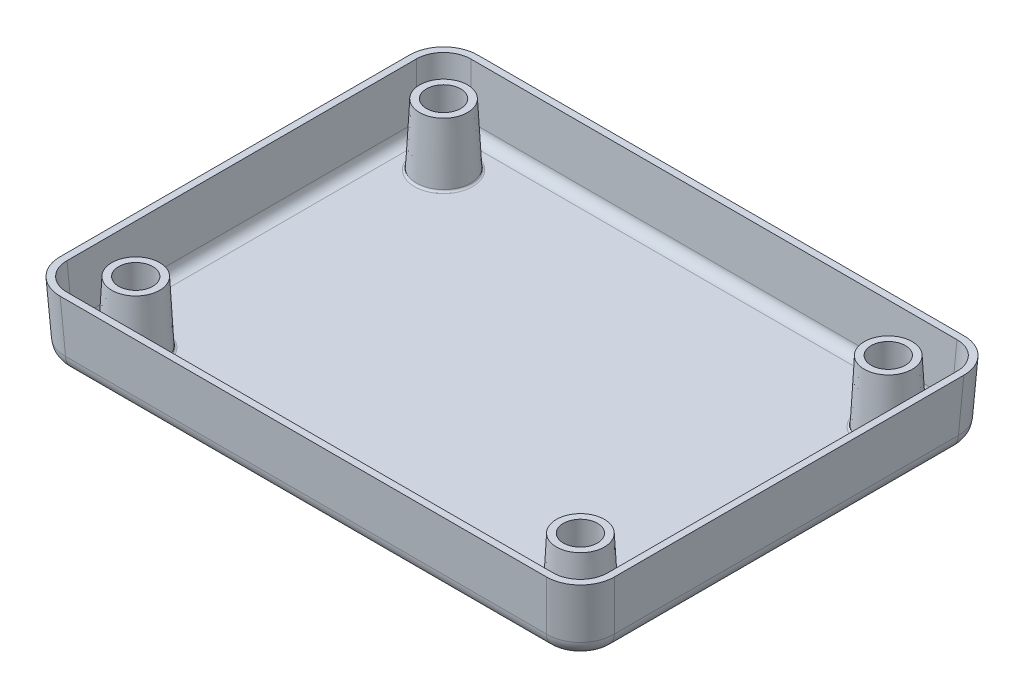
SolidWorks part; units mm, degrees
ref_plane "Front Plane" through (0, 0, 0) normal (0, 0, 1) x (1, 0, 0)
ref_plane "Top Plane" through (0, 0, 0) normal (0, 1, 0) x (1, 0, 0)
ref_plane "Right Plane" through (0, 0, 0) normal (1, 0, 0) x (0, 0, -1)
sketch "BOSS" plane through (0, 0, 0) normal (0, 1, 0) x (1, 0, 0)
  line L0 (82.55, 57.15) -> (101.6, 57.15) construction
  line L1 (0, 0) -> (101.6, 0)
  line L2 (0, 0) -> (0, 76.2)
  line L3 (0, 76.2) -> (101.6, 76.2)
  line L4 (101.6, 0) -> (101.6, 76.2)
  line L5 (82.55, 57.15) -> (82.55, 76.2) construction
  line L6 (0, 0) -> (0, -20.2965) construction
  line L7 (0, 0) -> (-16.6599, 0) construction
  circle A0 centre (82.55, 57.15) radius 6.35
  dimension "HOLE.SIZE" = 12.7
  dimension "EDGE.DISTANCE" = 19.05
  dimension "WIDTH" = 203.2
  dimension "HEIGHT" = 152.4
extrude "MAIN_BOSS" add sketch "BOSS" along normal blind 25.4
draft "Draft1" type of draft neutral plane draft angle 3 faces to draft 2 face at (50.8, 12.7, -76.2) face at (101.6, 12.7, -38.1) neutral plane through (0, 0, 0) neutral plane normal (0, -1, 0) parameters "D1"=3
draft "Draft2" type of draft neutral plane draft angle 3 faces to draft 1 face at (82.55, 25.4, -50.8) neutral plane through (0, 25.4, 0) neutral plane normal (0, 1, 0) reverse direction yes parameters "D1"=3
fillet "Fillet1" radius 12.7 1 edges at (102.2656, 12.7, -76.8656)
fillet "Fillet2" radius 6.35 3 edges at (44.4587, 0, -76.2) (97.8875, 0, -72.4875) (101.6, 0, -31.7587)
shell "Shell1" thickness 2.54 removed face at (59.7479, 25.4, -44.5079) removed face at (60.3242, 11.1105, 0) removed face at (0, 11.1105, -45.0842)
fillet "Fillet3" radius 0.762 1 edges at (82.55, 2.54, -67.2415)
fillet "Fillet4" radius 0.762 1 edges at (82.55, 0, -64.8312)
mirror "Mirror1" about plane through (0, 25.4, 0) normal (1, 0, 0) of bodies 101
mirror "Mirror2"
